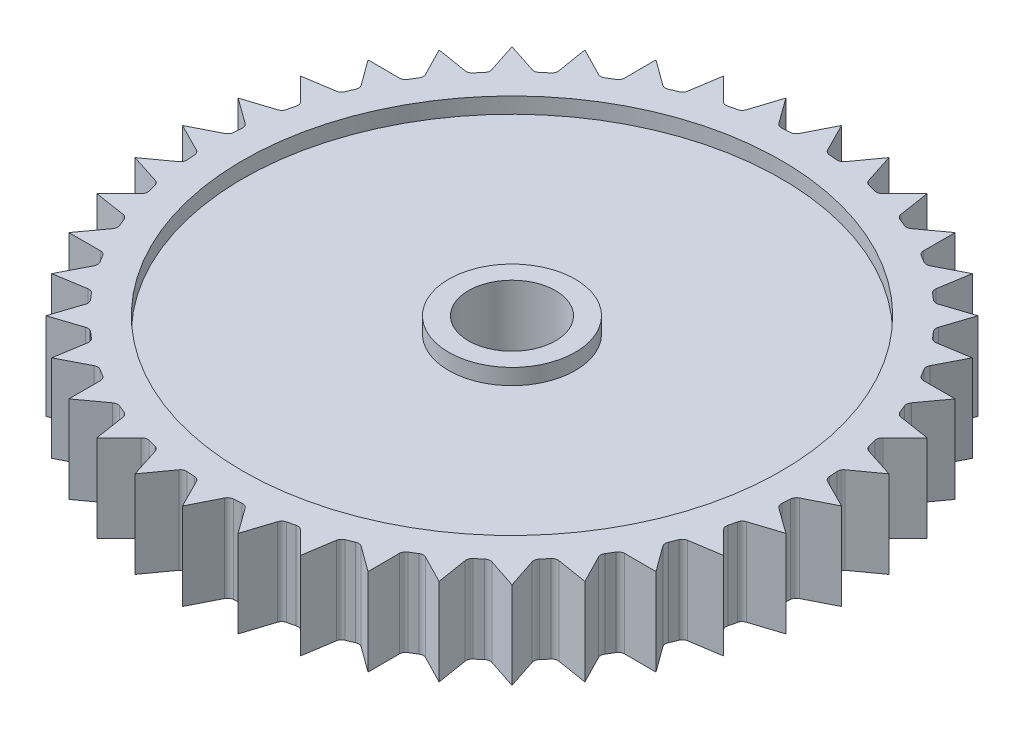
SolidWorks part; units mm, degrees
material "PET"
ref_plane "Front Plane" through (0, 0, 0) normal (0, 0, 1) x (1, 0, 0)
ref_plane "Top Plane" through (0, 0, 0) normal (0, 1, 0) x (1, 0, 0)
ref_plane "Right Plane" through (0, 0, 0) normal (1, 0, 0) x (0, 0, -1)
sketch "Sketch1" plane through (0, 0, 0) normal (0, 1, 0) x (1, 0, 0)
  line L0 (0, 0) -> (0, 23.81) construction
  line L1 (0, 0) -> (23.81, 0) construction
  line L2 (0, 0) -> (0, -23.81) construction
  line L3 (0, 0) -> (-23.81, 0) construction
  line L4 (0, 20.81) -> (-0.8962, 19.0386)
  line L5 (0, 20.81) -> (0.8962, 19.0386)
  line L6 (3.2554, 20.5538) -> (2.0931, 18.9444)
  line L7 (3.2554, 20.5538) -> (3.8635, 18.664)
  line L8 (6.4306, 19.7915) -> (5.0309, 18.3837)
  line L9 (6.4306, 19.7915) -> (6.7356, 17.8299)
  line L10 (9.4475, 18.5418) -> (7.8448, 17.3704)
  line L11 (9.4475, 18.5418) -> (9.4419, 16.5567)
  line L12 (12.2318, 16.8356) -> (10.4656, 15.9293)
  line L13 (12.2318, 16.8356) -> (11.9157, 14.8758)
  line L14 (14.7149, 14.7149) -> (12.8286, 14.096)
  line L15 (14.7149, 14.7149) -> (14.096, 12.8286)
  line L16 (16.8356, 12.2318) -> (14.8758, 11.9157)
  line L17 (16.8356, 12.2318) -> (15.9293, 10.4656)
  line L18 (18.5418, 9.4475) -> (16.5567, 9.4419)
  line L19 (18.5418, 9.4475) -> (17.3704, 7.8448)
  line L20 (19.7915, 6.4306) -> (17.8299, 6.7356)
  line L21 (19.7915, 6.4306) -> (18.3837, 5.0309)
  line L22 (20.5538, 3.2554) -> (18.664, 3.8635)
  line L23 (20.5538, 3.2554) -> (18.9444, 2.0931)
  line L24 (20.81, 0) -> (19.0386, 0.8962)
  line L25 (20.81, 0) -> (19.0386, -0.8962)
  line L26 (20.5538, -3.2554) -> (18.9444, -2.0931)
  line L27 (20.5538, -3.2554) -> (18.664, -3.8635)
  line L28 (19.7915, -6.4306) -> (18.3837, -5.0309)
  line L29 (19.7915, -6.4306) -> (17.8299, -6.7356)
  line L30 (18.5418, -9.4475) -> (17.3704, -7.8448)
  line L31 (18.5418, -9.4475) -> (16.5567, -9.4419)
  line L32 (16.8356, -12.2318) -> (15.9293, -10.4656)
  line L33 (16.8356, -12.2318) -> (14.8758, -11.9157)
  line L34 (14.7149, -14.7149) -> (14.096, -12.8286)
  line L35 (14.7149, -14.7149) -> (12.8286, -14.096)
  line L36 (12.2318, -16.8356) -> (11.9157, -14.8758)
  line L37 (12.2318, -16.8356) -> (10.4656, -15.9293)
  line L38 (9.4475, -18.5418) -> (9.4419, -16.5567)
  line L39 (9.4475, -18.5418) -> (7.8448, -17.3704)
  line L40 (6.4306, -19.7915) -> (6.7356, -17.8299)
  line L41 (6.4306, -19.7915) -> (5.0309, -18.3837)
  line L42 (3.2554, -20.5538) -> (3.8635, -18.664)
  line L43 (3.2554, -20.5538) -> (2.0931, -18.9444)
  line L44 (0, -20.81) -> (0.8962, -19.0386)
  line L45 (0, -20.81) -> (-0.8962, -19.0386)
  line L46 (-3.2554, -20.5538) -> (-2.0931, -18.9444)
  line L47 (-3.2554, -20.5538) -> (-3.8635, -18.664)
  line L48 (-6.4306, -19.7915) -> (-5.0309, -18.3837)
  line L49 (-6.4306, -19.7915) -> (-6.7356, -17.8299)
  line L50 (-9.4475, -18.5418) -> (-7.8448, -17.3704)
  line L51 (-9.4475, -18.5418) -> (-9.4419, -16.5567)
  line L52 (-12.2318, -16.8356) -> (-10.4656, -15.9293)
  line L53 (-12.2318, -16.8356) -> (-11.9157, -14.8758)
  line L54 (-14.7149, -14.7149) -> (-12.8286, -14.096)
  line L55 (-14.7149, -14.7149) -> (-14.096, -12.8286)
  line L56 (-16.8356, -12.2318) -> (-14.8758, -11.9157)
  line L57 (-16.8356, -12.2318) -> (-15.9293, -10.4656)
  line L58 (-18.5418, -9.4475) -> (-16.5567, -9.4419)
  line L59 (-18.5418, -9.4475) -> (-17.3704, -7.8448)
  line L60 (-19.7915, -6.4306) -> (-17.8299, -6.7356)
  line L61 (-19.7915, -6.4306) -> (-18.3837, -5.0309)
  line L62 (-20.5538, -3.2554) -> (-18.664, -3.8635)
  line L63 (-20.5538, -3.2554) -> (-18.9444, -2.0931)
  line L64 (-20.81, 0) -> (-19.0386, -0.8962)
  line L65 (-20.81, 0) -> (-19.0386, 0.8962)
  line L66 (-20.5538, 3.2554) -> (-18.9444, 2.0931)
  line L67 (-20.5538, 3.2554) -> (-18.664, 3.8635)
  line L68 (-19.7915, 6.4306) -> (-18.3837, 5.0309)
  line L69 (-19.7915, 6.4306) -> (-17.8299, 6.7356)
  line L70 (-18.5418, 9.4475) -> (-17.3704, 7.8448)
  line L71 (-18.5418, 9.4475) -> (-16.5567, 9.4419)
  line L72 (-16.8356, 12.2318) -> (-15.9293, 10.4656)
  line L73 (-16.8356, 12.2318) -> (-14.8758, 11.9157)
  line L74 (-14.7149, 14.7149) -> (-14.096, 12.8286)
  line L75 (-14.7149, 14.7149) -> (-12.8286, 14.096)
  line L76 (-12.2318, 16.8356) -> (-11.9157, 14.8758)
  line L77 (-12.2318, 16.8356) -> (-10.4656, 15.9293)
  line L78 (-9.4475, 18.5418) -> (-9.4419, 16.5567)
  line L79 (-9.4475, 18.5418) -> (-7.8448, 17.3704)
  line L80 (-6.4306, 19.7915) -> (-6.7356, 17.8299)
  line L81 (-6.4306, 19.7915) -> (-5.0309, 18.3837)
  line L82 (-3.2554, 20.5538) -> (-3.8635, 18.664)
  line L83 (-3.2554, 20.5538) -> (-2.0931, 18.9444)
  arc A0 (-1.2271, 18.82) -> (-1.7321, 18.7803) centre (0, 0) ccw
  circle A1 centre (0, 0) radius 20.81 construction
  arc A2 (0.8962, 19.0386) -> (1.2271, 18.82) centre (1.2531, 19.2192) ccw
  arc A3 (-0.8962, 19.0386) -> (-1.2271, 18.82) centre (-1.2531, 19.2192) cw
  arc A4 (2.0931, 18.9444) -> (1.7321, 18.7803) centre (1.7688, 19.1786) cw
  arc A5 (3.8635, 18.664) -> (4.1561, 18.3964) centre (4.2442, 18.7865) ccw
  arc A6 (5.0309, 18.3837) -> (4.6487, 18.2781) centre (4.7473, 18.6658) cw
  arc A7 (6.7356, 17.8299) -> (6.9828, 17.5197) centre (7.1309, 17.8913) ccw
  arc A8 (7.8448, 17.3704) -> (7.4508, 17.3259) centre (7.6088, 17.6933) cw
  arc A9 (9.4419, 16.5567) -> (9.6375, 16.2117) centre (9.8419, 16.5555) ccw
  arc A10 (10.4656, 15.9293) -> (10.0694, 15.947) centre (10.283, 16.2852) cw
  arc A11 (11.9157, 14.8758) -> (12.0549, 14.5045) centre (12.3106, 14.8121) ccw
  arc A12 (12.8286, 14.096) -> (12.4401, 14.1755) centre (12.7039, 14.4761) cw
  arc A13 (14.096, 12.8286) -> (14.1755, 12.4401) centre (14.4761, 12.7039) ccw
  arc A14 (14.8758, 11.9157) -> (14.5045, 12.0549) centre (14.8121, 12.3106) cw
  arc A15 (15.9293, 10.4656) -> (15.947, 10.0694) centre (16.2852, 10.283) ccw
  arc A16 (16.5567, 9.4419) -> (16.2117, 9.6375) centre (16.5555, 9.8419) cw
  arc A17 (17.3704, 7.8448) -> (17.3259, 7.4508) centre (17.6933, 7.6088) ccw
  arc A18 (17.8299, 6.7356) -> (17.5197, 6.9828) centre (17.8913, 7.1309) cw
  arc A19 (18.3837, 5.0309) -> (18.2781, 4.6487) centre (18.6658, 4.7473) ccw
  arc A20 (18.664, 3.8635) -> (18.3964, 4.1561) centre (18.7865, 4.2442) cw
  arc A21 (18.9444, 2.0931) -> (18.7803, 1.7321) centre (19.1786, 1.7688) ccw
  arc A22 (19.0386, 0.8962) -> (18.82, 1.2271) centre (19.2192, 1.2531) cw
  arc A23 (19.0386, -0.8962) -> (18.82, -1.2271) centre (19.2192, -1.2531) ccw
  arc A24 (18.9444, -2.0931) -> (18.7803, -1.7321) centre (19.1786, -1.7688) cw
  arc A25 (18.664, -3.8635) -> (18.3964, -4.1561) centre (18.7865, -4.2442) ccw
  arc A26 (18.3837, -5.0309) -> (18.2781, -4.6487) centre (18.6658, -4.7473) cw
  arc A27 (17.8299, -6.7356) -> (17.5197, -6.9828) centre (17.8913, -7.1309) ccw
  arc A28 (17.3704, -7.8448) -> (17.3259, -7.4508) centre (17.6933, -7.6088) cw
  arc A29 (16.5567, -9.4419) -> (16.2117, -9.6375) centre (16.5555, -9.8419) ccw
  arc A30 (15.9293, -10.4656) -> (15.947, -10.0694) centre (16.2852, -10.283) cw
  arc A31 (14.8758, -11.9157) -> (14.5045, -12.0549) centre (14.8121, -12.3106) ccw
  arc A32 (14.096, -12.8286) -> (14.1755, -12.4401) centre (14.4761, -12.7039) cw
  arc A33 (12.8286, -14.096) -> (12.4401, -14.1755) centre (12.7039, -14.4761) ccw
  arc A34 (11.9157, -14.8758) -> (12.0549, -14.5045) centre (12.3106, -14.8121) cw
  arc A35 (10.4656, -15.9293) -> (10.0694, -15.947) centre (10.283, -16.2852) ccw
  arc A36 (9.4419, -16.5567) -> (9.6375, -16.2117) centre (9.8419, -16.5555) cw
  arc A37 (7.8448, -17.3704) -> (7.4508, -17.3259) centre (7.6088, -17.6933) ccw
  arc A38 (6.7356, -17.8299) -> (6.9828, -17.5197) centre (7.1309, -17.8913) cw
  arc A39 (5.0309, -18.3837) -> (4.6487, -18.2781) centre (4.7473, -18.6658) ccw
  arc A40 (3.8635, -18.664) -> (4.1561, -18.3964) centre (4.2442, -18.7865) cw
  arc A41 (2.0931, -18.9444) -> (1.7321, -18.7803) centre (1.7688, -19.1786) ccw
  arc A42 (0.8962, -19.0386) -> (1.2271, -18.82) centre (1.2531, -19.2192) cw
  arc A43 (-0.8962, -19.0386) -> (-1.2271, -18.82) centre (-1.2531, -19.2192) ccw
  arc A44 (-2.0931, -18.9444) -> (-1.7321, -18.7803) centre (-1.7688, -19.1786) cw
  arc A45 (-3.8635, -18.664) -> (-4.1561, -18.3964) centre (-4.2442, -18.7865) ccw
  arc A46 (-5.0309, -18.3837) -> (-4.6487, -18.2781) centre (-4.7473, -18.6658) cw
  arc A47 (-6.7356, -17.8299) -> (-6.9828, -17.5197) centre (-7.1309, -17.8913) ccw
  arc A48 (-7.8448, -17.3704) -> (-7.4508, -17.3259) centre (-7.6088, -17.6933) cw
  arc A49 (-9.4419, -16.5567) -> (-9.6375, -16.2117) centre (-9.8419, -16.5555) ccw
  arc A50 (-10.4656, -15.9293) -> (-10.0694, -15.947) centre (-10.283, -16.2852) cw
  arc A51 (-11.9157, -14.8758) -> (-12.0549, -14.5045) centre (-12.3106, -14.8121) ccw
  arc A52 (-12.8286, -14.096) -> (-12.4401, -14.1755) centre (-12.7039, -14.4761) cw
  arc A53 (-14.096, -12.8286) -> (-14.1755, -12.4401) centre (-14.4761, -12.7039) ccw
  arc A54 (-14.8758, -11.9157) -> (-14.5045, -12.0549) centre (-14.8121, -12.3106) cw
  arc A55 (-15.9293, -10.4656) -> (-15.947, -10.0694) centre (-16.2852, -10.283) ccw
  arc A56 (-16.5567, -9.4419) -> (-16.2117, -9.6375) centre (-16.5555, -9.8419) cw
  arc A57 (-17.3704, -7.8448) -> (-17.3259, -7.4508) centre (-17.6933, -7.6088) ccw
  arc A58 (-17.8299, -6.7356) -> (-17.5197, -6.9828) centre (-17.8913, -7.1309) cw
  arc A59 (-18.3837, -5.0309) -> (-18.2781, -4.6487) centre (-18.6658, -4.7473) ccw
  arc A60 (-18.664, -3.8635) -> (-18.3964, -4.1561) centre (-18.7865, -4.2442) cw
  arc A61 (-18.9444, -2.0931) -> (-18.7803, -1.7321) centre (-19.1786, -1.7688) ccw
  arc A62 (-19.0386, -0.8962) -> (-18.82, -1.2271) centre (-19.2192, -1.2531) cw
  arc A63 (-19.0386, 0.8962) -> (-18.82, 1.2271) centre (-19.2192, 1.2531) ccw
  arc A64 (-18.9444, 2.0931) -> (-18.7803, 1.7321) centre (-19.1786, 1.7688) cw
  arc A65 (-18.664, 3.8635) -> (-18.3964, 4.1561) centre (-18.7865, 4.2442) ccw
  arc A66 (-18.3837, 5.0309) -> (-18.2781, 4.6487) centre (-18.6658, 4.7473) cw
  arc A67 (-17.8299, 6.7356) -> (-17.5197, 6.9828) centre (-17.8913, 7.1309) ccw
  arc A68 (-17.3704, 7.8448) -> (-17.3259, 7.4508) centre (-17.6933, 7.6088) cw
  arc A69 (-16.5567, 9.4419) -> (-16.2117, 9.6375) centre (-16.5555, 9.8419) ccw
  arc A70 (-15.9293, 10.4656) -> (-15.947, 10.0694) centre (-16.2852, 10.283) cw
  arc A71 (-14.8758, 11.9157) -> (-14.5045, 12.0549) centre (-14.8121, 12.3106) ccw
  arc A72 (-14.096, 12.8286) -> (-14.1755, 12.4401) centre (-14.4761, 12.7039) cw
  arc A73 (-12.8286, 14.096) -> (-12.4401, 14.1755) centre (-12.7039, 14.4761) ccw
  arc A74 (-11.9157, 14.8758) -> (-12.0549, 14.5045) centre (-12.3106, 14.8121) cw
  arc A75 (-10.4656, 15.9293) -> (-10.0694, 15.947) centre (-10.283, 16.2852) ccw
  arc A76 (-9.4419, 16.5567) -> (-9.6375, 16.2117) centre (-9.8419, 16.5555) cw
  arc A77 (-7.8448, 17.3704) -> (-7.4508, 17.3259) centre (-7.6088, 17.6933) ccw
  arc A78 (-6.7356, 17.8299) -> (-6.9828, 17.5197) centre (-7.1309, 17.8913) cw
  arc A79 (-5.0309, 18.3837) -> (-4.6487, 18.2781) centre (-4.7473, 18.6658) ccw
  arc A80 (-3.8635, 18.664) -> (-4.1561, 18.3964) centre (-4.2442, 18.7865) cw
  arc A81 (-2.0931, 18.9444) -> (-1.7321, 18.7803) centre (-1.7688, 19.1786) ccw
  arc A82 (-4.1561, 18.3964) -> (-4.6487, 18.2781) centre (0, 0) ccw
  arc A83 (-6.9828, 17.5197) -> (-7.4508, 17.3259) centre (0, 0) ccw
  arc A84 (-9.6375, 16.2117) -> (-10.0694, 15.947) centre (0, 0) ccw
  arc A85 (-12.0549, 14.5045) -> (-12.4401, 14.1755) centre (0, 0) ccw
  arc A86 (-14.1755, 12.4401) -> (-14.5045, 12.0549) centre (0, 0) ccw
  arc A87 (-15.947, 10.0694) -> (-16.2117, 9.6375) centre (0, 0) ccw
  arc A88 (-17.3259, 7.4508) -> (-17.5197, 6.9828) centre (0, 0) ccw
  arc A89 (-18.2781, 4.6487) -> (-18.3964, 4.1561) centre (0, 0) ccw
  arc A90 (-18.7803, 1.7321) -> (-18.82, 1.2271) centre (0, 0) ccw
  arc A91 (-18.82, -1.2271) -> (-18.7803, -1.7321) centre (0, 0) ccw
  arc A92 (-18.3964, -4.1561) -> (-18.2781, -4.6487) centre (0, 0) ccw
  arc A93 (-17.5197, -6.9828) -> (-17.3259, -7.4508) centre (0, 0) ccw
  arc A94 (-16.2117, -9.6375) -> (-15.947, -10.0694) centre (0, 0) ccw
  arc A95 (-14.5045, -12.0549) -> (-14.1755, -12.4401) centre (0, 0) ccw
  arc A96 (-12.4401, -14.1755) -> (-12.0549, -14.5045) centre (0, 0) ccw
  arc A97 (-10.0694, -15.947) -> (-9.6375, -16.2117) centre (0, 0) ccw
  arc A98 (-7.4508, -17.3259) -> (-6.9828, -17.5197) centre (0, 0) ccw
  arc A99 (-4.6487, -18.2781) -> (-4.1561, -18.3964) centre (0, 0) ccw
  arc A100 (-1.7321, -18.7803) -> (-1.2271, -18.82) centre (0, 0) ccw
  arc A101 (1.2271, -18.82) -> (1.7321, -18.7803) centre (0, 0) ccw
  arc A102 (4.1561, -18.3964) -> (4.6487, -18.2781) centre (0, 0) ccw
  arc A103 (6.9828, -17.5197) -> (7.4508, -17.3259) centre (0, 0) ccw
  arc A104 (9.6375, -16.2117) -> (10.0694, -15.947) centre (0, 0) ccw
  arc A105 (12.0549, -14.5045) -> (12.4401, -14.1755) centre (0, 0) ccw
  arc A106 (14.1755, -12.4401) -> (14.5045, -12.0549) centre (0, 0) ccw
  arc A107 (15.947, -10.0694) -> (16.2117, -9.6375) centre (0, 0) ccw
  arc A108 (17.3259, -7.4508) -> (17.5197, -6.9828) centre (0, 0) ccw
  arc A109 (18.2781, -4.6487) -> (18.82, -1.2271) centre (0, 0) ccw
  arc A110 (18.82, 1.2271) -> (18.7803, 1.7321) centre (0, 0) ccw
  arc A111 (18.3964, 4.1561) -> (18.2781, 4.6487) centre (0, 0) ccw
  arc A112 (17.5197, 6.9828) -> (17.3259, 7.4508) centre (0, 0) ccw
  arc A113 (16.2117, 9.6375) -> (15.947, 10.0694) centre (0, 0) ccw
  arc A114 (14.5045, 12.0549) -> (14.1755, 12.4401) centre (0, 0) ccw
  arc A115 (12.4401, 14.1755) -> (12.0549, 14.5045) centre (0, 0) ccw
  arc A116 (10.0694, 15.947) -> (9.6375, 16.2117) centre (0, 0) ccw
  arc A117 (7.4508, 17.3259) -> (6.9828, 17.5197) centre (0, 0) ccw
  arc A118 (4.6487, 18.2781) -> (4.1561, 18.3964) centre (0, 0) ccw
  arc A119 (1.7321, 18.7803) -> (1.2271, 18.82) centre (0, 0) ccw
  point P12 (1, 18.8335)
  point P15 (-1, 18.8335)
  point P291 (0, 0)
  dimension "D1" = 41.62
  dimension "D2" = 37.72
  dimension "D6" = 0.4
  dimension "D3" = 23.81
  dimension "D4" = 2
  dimension "D5" = 26.837
extrude "Boss-Extrude1" add sketch "Sketch1" along normal blind 5.5 contours A4 A119 A2 L5 L4 A3 A0 A81 L83 L82 A80 A82 A79 L81 L80 A78 A83 A77 L79 L78 A76 A84 A75 L77 L76 A74 A85 A73 L75 L74 A72 A86 A71 L73 L72 A70 A87 A69 L71 L70 A68 A88 A67 L69 L68 A66 A89 A65 L67 L66 A64 region at (-0.0316, 0, -0.005)
sketch "Sketch2" plane through (0, 5.5, 0) normal (0, 1, 0) x (1, 0, 0)
  circle A0 centre (0, 0) radius 4
  circle A1 centre (0, 0) radius 17
  circle A2 centre (0, 0) radius 2.75
  dimension "D1" = 34
  dimension "D2" = 8
  dimension "D3" = 5.5
extrude "Cut-Extrude1" cut sketch "Sketch2" against normal through all contours A2 region at (0, 5.5, 0)
extrude "Cut-Extrude2" cut sketch "Sketch2<3>" against normal blind 1 contours A1 A0 region at (-16.5192, 5.5, 0)
sketch "Sketch2<3>" plane through (0, 5.5, 0) normal (0, 1, 0) x (1, 0, 0) same geometry as "Sketch2"
sketch "Sketch4" plane through (0, 0, 0) normal (0, -1, 0) x (1, 0, 0)
  circle A0 centre (0, 0) radius 4
  circle A1 centre (0, 0) radius 17
  dimension "D1" = 34
  dimension "D2" = 8
extrude "Cut-Extrude4" cut sketch "Sketch4" against normal blind 1
extrude "Boss-Extrude2" add sketch "Sketch1<3>" along normal blind 5.5 contours A109 A25 L27 L26 A24 region at (19.2586, 0, 3.0503)
sketch "Sketch1<3>" plane through (0, 0, 0) normal (0, 1, 0) x (1, 0, 0) same geometry as "Sketch1"
sketch "Sketch5" plane through (0, 5.5, 0) normal (0, 1, 0) x (1, 0, 0)
  circle A0 centre (0, 0) radius 20
  dimension "D1" = 40
